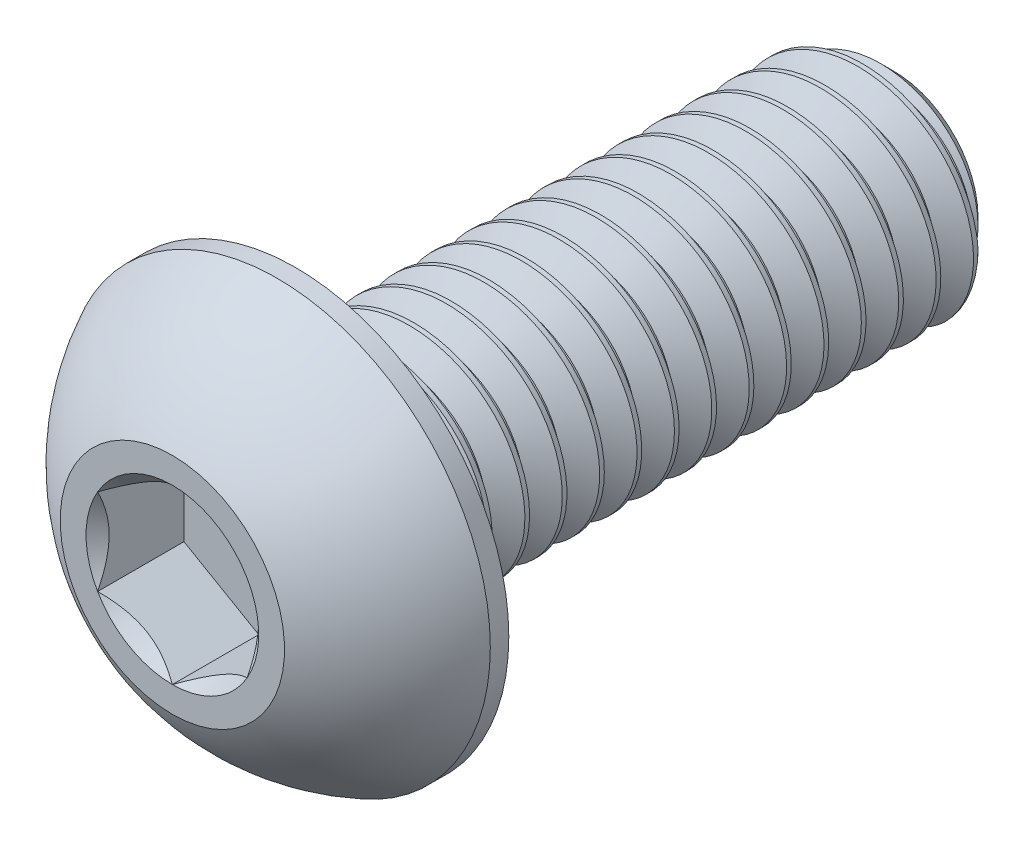
SolidWorks part; units mm, degrees
ref_plane "Front" through (0, 0, 0) normal (0, 0, 1) x (1, 0, 0)
ref_plane "Top" through (0, 0, 0) normal (0, 1, 0) x (1, 0, 0)
ref_plane "Right" through (0, 0, 0) normal (1, 0, 0) x (0, 0, -1)
sketch "Sketch1" plane through (0, 0, 0) normal (1, 0, 0) x (0, 0, -1)
  line L2 (1.65, 1.5) -> (9.65, 1.5)
  line L3 (9.65, 1.5) -> (9.65, 0)
  line L4 (9.65, 0) -> (1.65, 0)
  line L6 (1.4025, 2.85) -> (1.65, 2.85) construction
  line L7 (9.65, 1.5) -> (9.65, -1.5) construction
  line L8 (0, 0) -> (1.65, 0) construction
  line L9 (1.65, 2.85) -> (1.65, -2.85) construction
  line L11 (1.65, 1.5) -> (1.65, 0)
  line L13 (0, 1) -> (0, -1) construction
  line L14 (0, 1) -> (0, 1.5) construction
  line L15 (9.6187, 1.5541) -> (9.8687, 1.1211) construction
  line L16 (9.8687, 1.1211) -> (10.1187, 1.5541) construction
  line L17 (10.1187, 1.5541) -> (9.6187, 1.5541) construction
  line L18 (9.65, 1.5) -> (10.0875, 1.5) construction
  line L19 (9.8687, 1.5541) -> (9.8687, 1.5) construction
  line L20 (9.8687, 1.5) -> (9.8687, 1.1752) construction
  line L21 (9.8687, 1.1752) -> (9.8687, 1.1211) construction
  line L22 (9.8375, 1.1752) -> (9.9, 1.1752)
  line L23 (9.6344, 1.5271) -> (10.1031, 1.5271)
  line L24 (9.9, 1.1752) -> (10.1031, 1.5271)
  line L25 (9.8375, 1.1752) -> (9.6344, 1.5271)
  line L26 (9.275, 1.5) -> (9.65, 1.125)
  arc A3 (0, 1.5) -> (1.4025, 2.85) centre (2.7948, 0) cw construction
  point P29 (9.8687, 1.5271)
  point P30 (8.4, -1.5)
  dimension "D1" = 0.2475
  dimension "Pitch" = 0.5
  dimension "D3" = 0.0625
  dimension "D2" = 0.375
  dimension "D4" = 45
  dimension "D5" = 1.25
sketch "Sketch10" plane through (0, 0, 0) normal (1, 0, 0) x (0, 0, -1)
  line L0 (9.275, 1.5) -> (9.65, 1.125) construction
  line L1 (9.275, 1.5) -> (9.65, 1.125)
  line L4 (9.65, 1.5) -> (1.65, 1.5)
  line L5 (9.65, 0) -> (9.65, 1.5)
  line L6 (1.65, 0) -> (9.65, 0)
  line L7 (1.65, 1.5) -> (1.65, 0)
  line L8 (9.275, 1.5) -> (1.65, 1.5)
  line L9 (9.65, 0) -> (9.65, 1.125)
  line L10 (1.65, 0) -> (9.65, 0)
  line L11 (1.65, 1.5) -> (1.65, 0)
  dimension "D1" = 0
revolve "Revolve3" add sketch "Sketch10" angle 360 about L8
sketch "Sketch7" plane through (0, 0, 0) normal (1, 0, 0) x (0, 0, -1)
  line L6 (1.4025, 2.85) -> (1.65, 2.85) construction
  line L8 (0, 0) -> (1.65, 0) construction
  line L11 (1.65, 2.85) -> (1.65, -2.85) construction
  line L12 (1.4025, 2.85) -> (1.65, 2.85)
  line L13 (0, 0) -> (1.65, 0)
  line L14 (0, 1) -> (0, -1) construction
  line L15 (1.65, 2.85) -> (1.65, 0)
  line L16 (0, 1.5) -> (0, 0)
  arc A2 (1.4025, 2.85) -> (0, 1.5) centre (2.7948, 0) ccw construction
  arc A3 (1.4025, 2.85) -> (0, 1.5) centre (2.7948, 0) ccw
revolve "Revolve2" add sketch "Sketch7" angle 360 mid plane about L13
sketch "Sketch5" plane through (0, 0, 0) normal (0, 0, 1) x (1, 0, 0)
  line L1 (1, -0.5774) -> (1, 0.5774)
  line L2 (1, 0.5774) -> (0, 1.1547)
  line L3 (0, 1.1547) -> (-1, 0.5774)
  line L4 (-1, 0.5774) -> (-1, -0.5774)
  line L5 (-1, -0.5774) -> (0, -1.1547)
  line L6 (0, -1.1547) -> (1, -0.5774)
  circle A0 centre (0, 0) radius 1 construction
extrude "Cut-Extrude2" cut sketch "Sketch5" against normal blind 1.155
sketch "Sketch6" plane through (0, 0, 0) normal (0, 0, 1) x (1, 0, 0)
  circle A0 centre (0, 0) radius 1.1547
extrude "Cut-Extrude3" cut sketch "Sketch6" against normal blind 1.155 draft 45
sketch "Sketch9" plane through (0, 0, -1.65) normal (0, 0, -1) x (-1, 0, 0)
  circle A0 centre (0, 0) radius 1.5 construction
  circle A4 centre (0, 0) radius 1.5
split "Split1" bodies to split 113 resulting bodies 123 124 split by face at (2.85, 0, -1.65)
sketch "Sketch11" plane through (0, 0, -9.65) normal (0, 0, -1) x (-1, 0, 0)
  circle A0 centre (0, 0) radius 1.5 construction
  circle A1 centre (0, 0) radius 1.5
curve "Helix/Spiral1" pitch 0.5 height 9.65 radius 1.5 centre (0, 0, -9.65) axis (0, 0, 1) start towards (0, 1, 0)
sketch "Sketch12" plane through (0, 0, 0) normal (1, 0, 0) x (0, 0, -1)
  line L0 (9.8375, 1.1752) -> (9.9, 1.1752) construction
  line L1 (9.9, 1.1752) -> (10.1031, 1.5271) construction
  line L2 (9.6344, 1.5271) -> (10.1031, 1.5271) construction
  line L3 (9.8375, 1.1752) -> (9.6344, 1.5271) construction
  line L4 (9.8375, 1.1752) -> (9.9, 1.1752)
  line L5 (9.9, 1.1752) -> (10.1031, 1.5271)
  line L6 (9.6344, 1.5271) -> (10.1031, 1.5271)
  line L7 (9.8375, 1.1752) -> (9.6344, 1.5271)
sweep "Cut-Sweep2" cut profiles "Sketch12" path "Helix/Spiral1" align with end faces yes
extrude "Boss-Extrude1" add sketch "Sketch9" along normal blind 10 draft 45
equation "\"D1@Cut-Extrude2\" = \"Head Ht@Sketch1\" * .7"
equation "\"D1@Sketch1\" = \"Head Ht@Sketch1\" * .15"
equation "\"D1@Cut-Extrude3\" = \"D1@Cut-Extrude2\""
equation "\"D3@Sketch1\" = \"Pitch@Sketch1\" / 8"
equation "\"D2@Sketch1\"=\"Pitch@Sketch1\"*0.75"
equation "\"D3@Helix/Spiral1\" = \"Lg@Sketch1\" + \"Head Ht@Sketch1\""
equation "\"D4@Helix/Spiral1\"=\"pitch@sketch1\""
equation "\"D5@Sketch1\"=\"Pitch@Sketch1\"*2.5"
